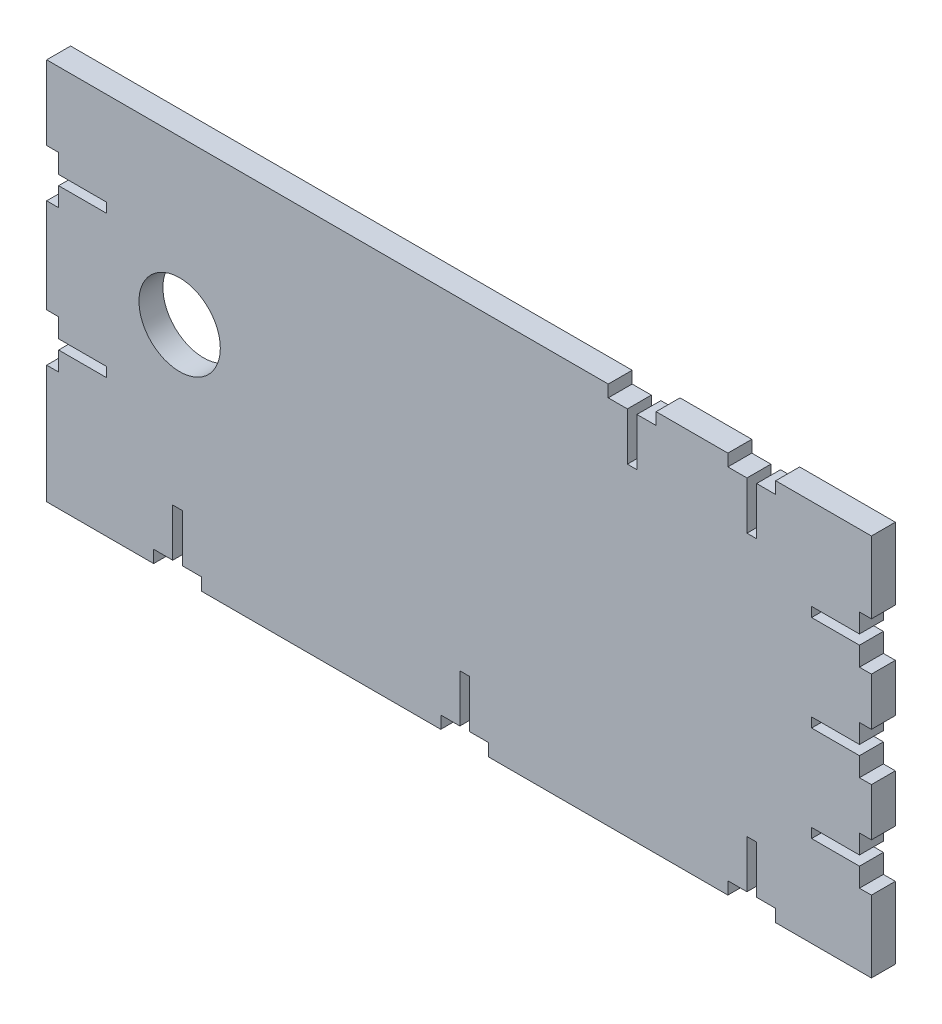
SolidWorks part; units mm, degrees
ref_plane "Front Plane" through (0, 0, 0) normal (0, 0, 1) x (1, 0, 0)
ref_plane "Top Plane" through (0, 0, 0) normal (0, 1, 0) x (1, 0, 0)
ref_plane "Right Plane" through (0, 0, 0) normal (1, 0, 0) x (0, 0, -1)
sketch "Sketch1" plane through (0, 0, 0) normal (0, 0, 1) x (1, 0, 0)
  line L0 (0, 0) -> (127, 0)
  line L1 (127, 0) -> (127, 101.6)
  line L3 (0, 101.6) -> (0, 0) construction
  line L4 (0, 101.6) -> (-70.6924, 172.2924)
  line L5 (-70.6924, 172.2924) -> (-91.8969, 151.088)
  line L6 (-91.8969, 151.088) -> (-91.8969, 0)
  line L7 (-91.8969, 0) -> (0, 0)
  line L8 (127, 101.6) -> (0, 101.6)
  dimension "D1" = 127
  dimension "D2" = 101.6
  dimension "D3" = 135
  dimension "D4" = 29.9876
  dimension "D5" = 151.088
extrude "Boss-Extrude1" add sketch "Sketch1" along normal blind 6.35
sketch "Sketch2" plane through (0, 0, 0) normal (0, 0, -1) x (-1, 0, 0)
  line L0 (0, 101.6) -> (-25.4, 101.6) construction
  line L1 (-127, 101.6) -> (0, 101.6) construction
  line L2 (-25.4, 101.6) -> (-31.75, 101.6)
  line L3 (-25.4, 101.6) -> (-61.321, 65.679)
  line L4 (-31.75, 101.6) -> (-67.671, 65.679)
  line L5 (-67.671, 65.679) -> (-61.321, 65.679)
  line L6 (-49.7105, 83.6395) -> (-43.3605, 83.6395) construction
  line L7 (-31.75, 101.6) -> (-49.7105, 83.6395)
  dimension "D1" = 25.4
  dimension "D2" = 6.35
  dimension "D3" = 50.8
  dimension "D4" = 45
  dimension "D5" = 45
  dimension "D6" = 50.8
  dimension "D7" = 135
  dimension "D8" = 25.4
sketch "Sketch3" plane through (0, 0, 0) normal (0, 0, -1) x (-1, 0, 0)
  line L0 (70.6924, 172.2924) -> (61.7122, 163.3122) construction
  line L1 (0, 101.6) -> (70.6924, 172.2924) construction
  line L2 (59.4671, 161.0671) -> (63.9572, 165.5572)
  line L3 (59.4671, 161.0671) -> (63.9572, 156.577) construction
  line L5 (68.4474, 161.0671) -> (63.9572, 165.5572) construction
  line L6 (70.6924, 172.2924) -> (91.8969, 151.088) construction
  line L7 (63.9572, 156.577) -> (68.4474, 161.0671)
  line L8 (63.9572, 156.577) -> (66.2023, 154.3319)
  line L9 (68.4474, 161.0671) -> (70.6924, 158.822)
  line L10 (70.6924, 158.822) -> (66.2023, 154.3319)
  line L11 (-127, 25.4) -> (-127, 0)
  line L12 (-127, 50.8) -> (-127, 101.6) construction
  line L13 (-127, 0) -> (-127, 50.8) construction
  line L14 (-25.4, 0) -> (-12.7, 0)
  line L15 (-127, 82.55) -> (-127, 69.85)
  line L16 (0, 101.6) -> (-63.5, 101.6) construction
  line L17 (-127, 44.45) -> (-127, 57.15)
  line L18 (-127, 19.05) -> (-127, 31.75)
  line L19 (-63.5, 101.6) -> (-127, 101.6) construction
  line L20 (-101.6, 101.6) -> (-88.9, 101.6)
  line L21 (-69.85, 101.6) -> (-57.15, 101.6)
  line L22 (70.6924, 172.2924) -> (0, 101.6) construction
  line L23 (30.8561, 132.4561) -> (39.8363, 141.4363)
  line L24 (91.8969, 119.666) -> (91.8969, 106.966)
  line L25 (91.8969, 0) -> (91.8969, 75.544) construction
  line L26 (91.8969, 75.544) -> (91.8969, 151.088) construction
  line L27 (91.8969, 81.894) -> (91.8969, 69.194)
  line L28 (91.8969, 44.122) -> (91.8969, 31.422)
  line L29 (30.8561, 132.4561) -> (33.1011, 130.211)
  line L30 (-127, 82.55) -> (-123.825, 82.55)
  line L31 (-127, 82.55) -> (-127, 69.85)
  line L32 (-127, 69.85) -> (-123.825, 69.85)
  line L33 (-123.825, 82.55) -> (-123.825, 69.85) construction
  line L34 (-127, 57.15) -> (-123.825, 57.15)
  line L35 (-127, 57.15) -> (-127, 44.45)
  line L36 (-127, 44.45) -> (-123.825, 44.45)
  line L37 (-123.825, 57.15) -> (-123.825, 44.45) construction
  line L38 (-127, 31.75) -> (-123.825, 31.75)
  line L39 (-127, 31.75) -> (-127, 19.05)
  line L40 (-127, 19.05) -> (-123.825, 19.05)
  line L41 (-123.825, 31.75) -> (-123.825, 19.05) construction
  line L42 (-101.6, 101.6) -> (-88.9, 101.6)
  line L43 (-101.6, 101.6) -> (-101.6, 98.425)
  line L44 (-101.6, 98.425) -> (-88.9, 98.425) construction
  line L45 (-88.9, 101.6) -> (-88.9, 98.425)
  line L46 (-69.85, 101.6) -> (-57.15, 101.6)
  line L47 (-69.85, 101.6) -> (-69.85, 98.425)
  line L48 (-69.85, 98.425) -> (-57.15, 98.425) construction
  line L49 (-57.15, 101.6) -> (-57.15, 98.425)
  line L54 (39.8363, 141.4363) -> (42.0814, 139.1913)
  line L55 (42.0814, 139.1913) -> (33.1011, 130.211)
  line L56 (-123.825, 77.4827) -> (-123.825, 74.9173) construction
  line L57 (91.8969, 119.666) -> (88.7219, 119.666)
  line L58 (91.8969, 119.666) -> (91.8969, 106.966)
  line L59 (91.8969, 106.966) -> (88.7219, 106.966)
  line L60 (88.7219, 119.666) -> (88.7219, 106.966) construction
  line L61 (91.8969, 81.894) -> (88.7219, 81.894)
  line L62 (91.8969, 81.894) -> (91.8969, 69.194)
  line L63 (91.8969, 69.194) -> (88.7219, 69.194)
  line L64 (88.7219, 81.894) -> (88.7219, 69.194) construction
  line L65 (91.8969, 44.122) -> (88.7219, 44.122)
  line L66 (91.8969, 44.122) -> (91.8969, 31.422)
  line L67 (91.8969, 31.422) -> (88.7219, 31.422)
  line L68 (88.7219, 44.122) -> (88.7219, 31.422) construction
  line L69 (-101.6, 0) -> (-101.6, 3.302)
  line L70 (-123.825, 77.4827) -> (-111.125, 77.4827)
  line L71 (-123.825, 77.4827) -> (-123.825, 74.9173) construction
  line L72 (-123.825, 74.9173) -> (-111.125, 74.9173)
  line L73 (-111.125, 77.4827) -> (-111.125, 74.9173)
  line L74 (91.8969, 0) -> (-127, 0) construction
  line L75 (-101.6, 3.302) -> (-88.9, 3.302) construction
  line L76 (-88.9, 3.302) -> (-88.9, 0)
  line L77 (-101.6, 0) -> (-88.9, 0)
  line L78 (-25.4, 0) -> (-25.4, 3.302)
  line L79 (-25.4, 3.302) -> (-12.7, 3.302) construction
  line L80 (-12.7, 3.302) -> (-12.7, 0)
  line L81 (50.8, 0) -> (50.8, 3.302)
  line L82 (50.8, 3.302) -> (63.5, 3.302) construction
  line L83 (63.5, 3.302) -> (63.5, 0)
  line L84 (63.5, 0) -> (50.8, 0)
  line L85 (-93.9673, 3.302) -> (-96.5327, 3.302) construction
  line L86 (-96.5327, 3.302) -> (-96.5327, 16.002)
  line L87 (-96.5327, 16.002) -> (-93.9673, 16.002)
  line L88 (-93.9673, 16.002) -> (-93.9673, 3.302)
  line L89 (-17.7673, 3.302) -> (-20.3327, 3.302) construction
  line L90 (-20.3327, 3.302) -> (-20.3327, 16.002)
  line L91 (-20.3327, 16.002) -> (-17.7673, 16.002)
  line L92 (-17.7673, 16.002) -> (-17.7673, 3.302)
  line L93 (58.4327, 3.302) -> (55.8673, 3.302) construction
  line L94 (55.8673, 3.302) -> (55.8673, 16.002)
  line L95 (55.8673, 16.002) -> (58.4327, 16.002)
  line L96 (58.4327, 16.002) -> (58.4327, 3.302)
  line L97 (-123.825, 24.1173) -> (-123.825, 26.6827) construction
  line L98 (-123.825, 26.6827) -> (-111.125, 26.6827)
  line L99 (-111.125, 26.6827) -> (-111.125, 24.1173)
  line L100 (-111.125, 24.1173) -> (-123.825, 24.1173)
  line L101 (-123.825, 49.5173) -> (-123.825, 52.0827) construction
  line L102 (-123.825, 52.0827) -> (-111.125, 52.0827)
  line L103 (-111.125, 52.0827) -> (-111.125, 49.5173)
  line L104 (-111.125, 49.5173) -> (-123.825, 49.5173)
  line L105 (-93.9673, 98.425) -> (-96.5327, 98.425) construction
  line L106 (-96.5327, 98.425) -> (-96.5327, 85.725)
  line L107 (-96.5327, 85.725) -> (-93.9673, 85.725)
  line L108 (-93.9673, 85.725) -> (-93.9673, 98.425)
  line L109 (-62.23, 98.425) -> (-64.77, 98.425) construction
  line L110 (-64.77, 98.425) -> (-64.77, 85.725)
  line L111 (-64.77, 85.725) -> (-62.23, 85.725)
  line L112 (-62.23, 85.725) -> (-62.23, 98.425)
  line L113 (88.7219, 112.0333) -> (88.7219, 114.5987) construction
  line L114 (88.7219, 114.5987) -> (76.0219, 114.5987)
  line L115 (76.0219, 114.5987) -> (76.0219, 112.0333)
  line L116 (76.0219, 112.0333) -> (88.7219, 112.0333)
  line L117 (88.7219, 74.2613) -> (88.7219, 76.8267) construction
  line L118 (88.7219, 76.8267) -> (76.0219, 76.8267)
  line L119 (76.0219, 76.8267) -> (76.0219, 74.2613)
  line L120 (76.0219, 74.2613) -> (88.7219, 74.2613)
  line L121 (88.7219, 36.4893) -> (88.7219, 39.0547) construction
  line L122 (88.7219, 39.0547) -> (76.0219, 39.0547)
  line L123 (76.0219, 39.0547) -> (76.0219, 36.4893)
  line L124 (76.0219, 36.4893) -> (88.7219, 36.4893)
  line L125 (-123.825, 44.45) -> (-123.825, 49.5173)
  line L126 (-123.825, 52.0827) -> (-123.825, 57.15) construction
  line L127 (-123.825, 82.55) -> (-123.825, 77.4827)
  line L128 (-123.825, 74.9173) -> (-123.825, 69.85)
  line L129 (-123.825, 57.15) -> (-123.825, 52.0827)
  line L130 (-123.825, 52.0827) -> (-123.825, 57.15)
  line L131 (-123.825, 26.6827) -> (-123.825, 31.75)
  line L132 (-123.825, 19.05) -> (-123.825, 24.1173)
  line L133 (-101.6, 3.302) -> (-96.5327, 3.302)
  line L135 (-101.6, 98.425) -> (-96.5327, 98.425)
  line L136 (-93.9673, 98.425) -> (-88.9, 98.425)
  line L137 (-64.77, 98.425) -> (-69.85, 98.425)
  line L138 (-62.23, 98.425) -> (-57.15, 98.425)
  line L139 (-93.9673, 3.302) -> (-88.9, 3.302)
  line L140 (-25.4, 3.302) -> (-20.3327, 3.302)
  line L141 (-17.7673, 3.302) -> (-12.7, 3.302)
  line L142 (50.8, 3.302) -> (55.8673, 3.302)
  line L143 (58.4327, 3.302) -> (63.5, 3.302)
  line L144 (88.7219, 39.0547) -> (88.7219, 44.122)
  line L145 (88.7219, 31.422) -> (88.7219, 36.4893)
  line L146 (88.7219, 69.194) -> (88.7219, 74.2613)
  line L147 (88.7219, 76.8267) -> (88.7219, 81.894)
  line L148 (88.7219, 106.966) -> (88.7219, 112.0333)
  line L149 (88.7219, 114.5987) -> (88.7219, 119.666)
  point P8 (61.7122, 163.3122)
  point P27 (-127, 76.2)
  point P30 (-127, 50.8)
  point P33 (-127, 25.4)
  point P34 (-95.25, 101.6)
  point P36 (-95.25, 101.6)
  point P39 (-63.5, 85.725)
  point P41 (-31.75, 101.6)
  point P42 (-63.5, 101.6)
  point P45 (35.3462, 136.9462)
  point P53 (91.8969, 113.316)
  point P56 (91.8969, 75.544)
  point P59 (91.8969, 37.772)
  point P70 (-95.25, 3.302)
  point P82 (-123.825, 76.2)
  point P102 (-19.05, 3.302)
  point P107 (57.15, 3.302)
  point P112 (-123.825, 25.4)
  point P117 (-123.825, 50.8)
  point P122 (-95.25, 98.425)
  point P127 (-63.5, 98.425)
  point P132 (88.7219, 113.316)
  point P137 (88.7219, 75.544)
  point P142 (88.7219, 37.772)
  line M40 (-127, 0) -> (91.8969, 0)
  line M41 (91.8969, 0) -> (91.8969, 151.088)
  line M44 (0, 101.6) -> (-127, 101.6)
  line M45 (-127, 101.6) -> (-127, 0)
  dimension "D1" = 12.7
  dimension "D2" = 9.525
  dimension "D3" = 6.35
  dimension "D4" = 6.35
  dimension "D5" = 6.35
  dimension "D6" = 3.175
  dimension "D7" = 3.175
  dimension "D8" = 12.7
  dimension "D9" = 12.7
  dimension "D10" = 12.7
  dimension "D11" = 25.4
  dimension "D12" = 12.7
  dimension "D13" = 12.7
  dimension "D14" = 12.7
  dimension "D15" = 31.75
  dimension "D16" = 12.7
  dimension "D17" = 75.544
  dimension "D18" = 12.7
  dimension "D19" = 12.7
  dimension "D20" = 12.7
  dimension "D21" = 3.175
  dimension "D22" = 3.175
  dimension "D23" = 3.175
  dimension "D24" = 3.175
  dimension "D25" = 3.175
  dimension "D26" = 3.302
  dimension "D27" = 3.175
  dimension "D28" = 3.175
  dimension "D29" = 12.7
  dimension "D30" = 3.175
  dimension "D31" = 3.175
  dimension "D32" = 3.175
  dimension "D33" = 2.5654
  dimension "D34" = 12.7
  dimension "D35" = 25.4
  dimension "D36" = 63.5
  dimension "D37" = 63.5
  dimension "D38" = 3.302
  dimension "D39" = 12.7
  dimension "D40" = 12.7
  dimension "D41" = 3.302
  dimension "D42" = 2.5654
  dimension "D43" = 12.7
  dimension "D44" = 12.7
  dimension "D45" = 2.5654
  dimension "D46" = 12.7
  dimension "D47" = 2.5654
  dimension "D48" = 12.7
  dimension "D49" = 2.5654
  dimension "D50" = 12.7
  dimension "D51" = 1.27
  dimension "D52" = 12.7
  dimension "D53" = 2.5654
  dimension "D54" = 2.5654
  dimension "D55" = 12.7
  dimension "D56" = 2.5654
  dimension "D57" = 12.7
  dimension "D58" = 12.7
  dimension "D59" = 2.5654
  dimension "D60" = 12.7
  dimension "D61" = 2.5654
extrude "Cut-Extrude4" cut sketch "Sketch3" against normal blind 127 and the other way blind 127 contours L108 L136 L45 L43 L135 L106 L107 M44 | L112 L138 L49 L47 L137 L110 L111 M44 | L128 L72 L73 L70 L127 L30 L32 M45 | L129 L34 L36 L125 L104 L103 L102 M45 | L40 L132 L100 L99 L98 L131 L38 M45 | L139 L88 L87 L86 L133 L69 L76 M40 | L141 L92 L91 L90 L140 L78 L80 M40 | L143 L96 L95 L94 L142 L81 L83 M40 | L145 L67 L65 L144 L122 L123 L124 M41 | L147 L118 L119 L120 L146 L63 L61 M41 | L149 L114 L115 L116 L148 L59 L57 M41 | L10 L9 L7 L8 region at (-67.3248, 157.6995, 0) region at (121.8652, 25.4, 0) region at (63.5, 96.4847, 0) region at (95.25, 96.4652, 0) region at (121.8652, 76.2, 0) region at (121.8652, 50.8, 0) region at (-86.7621, 113.316, 0) region at (-86.7621, 75.544, 0) region at (-86.7621, 37.772, 0) region at (-57.15, 5.1493, 0) region at (19.05, 5.1493, 0) region at (95.25, 5.1493, 0)
sketch "Sketch4" plane through (0, 0, 0) normal (0, 0, 1) x (1, 0, 0)
  line L0 (-81.9177, 147.5967) -> (-79.6727, 149.8418)
  line L1 (-81.9177, 147.5967) -> (-77.4276, 143.1066)
  line L2 (-77.4276, 143.1066) -> (-75.1826, 145.3517)
  line L3 (-75.1826, 145.3517) -> (-79.6727, 149.8418)
  line L5 (-70.6924, 158.822) -> (-66.2023, 154.3319) construction
  line L6 (-70.6924, 172.2924) -> (-91.8969, 151.088) construction
  dimension "D1" = 3.175
  dimension "D2" = 6.35
  dimension "D3" = 12.7
  dimension "D4" = 9.525
extrude "Cut-Extrude5" cut sketch "Sketch4" against normal blind 127 and the other way blind 127 contours L0 L3 L2 L1
sketch "Sketch5" plane through (0, 0, 0) normal (0, 0, 1) x (1, 0, 0)
  line L1 (127, 101.6) -> (-102.8084, 101.6)
  line L2 (127, 101.6) -> (127, 179.517)
  line L3 (127, 179.517) -> (-102.8084, 179.517)
  line L4 (-102.8084, 101.6) -> (-102.8084, 179.517)
extrude "Cut-Extrude7" cut sketch "Sketch5" against normal blind 127 and the other way blind 127
ref_plane "Plane1" through (0, 0, -2.54) normal (0, 0, -1) x (-1, 0, 0)
sketch "Sketch6" plane through (0, 0, -2.54) normal (0, 0, -1) x (-1, 0, 0)
  line L0 (-57.15, 101.6) -> (91.8969, 101.6) construction
  line L1 (91.8969, 69.194) -> (91.8969, 44.122) construction
  circle A0 centre (56.6019, 58.3543) radius 10.795
  dimension "D1" = 21.59
  dimension "D2" = 43.2457
  dimension "D3" = 35.295
extrude "Cut-Extrude8" cut sketch "Sketch6" against normal blind 127 and the other way blind 127
